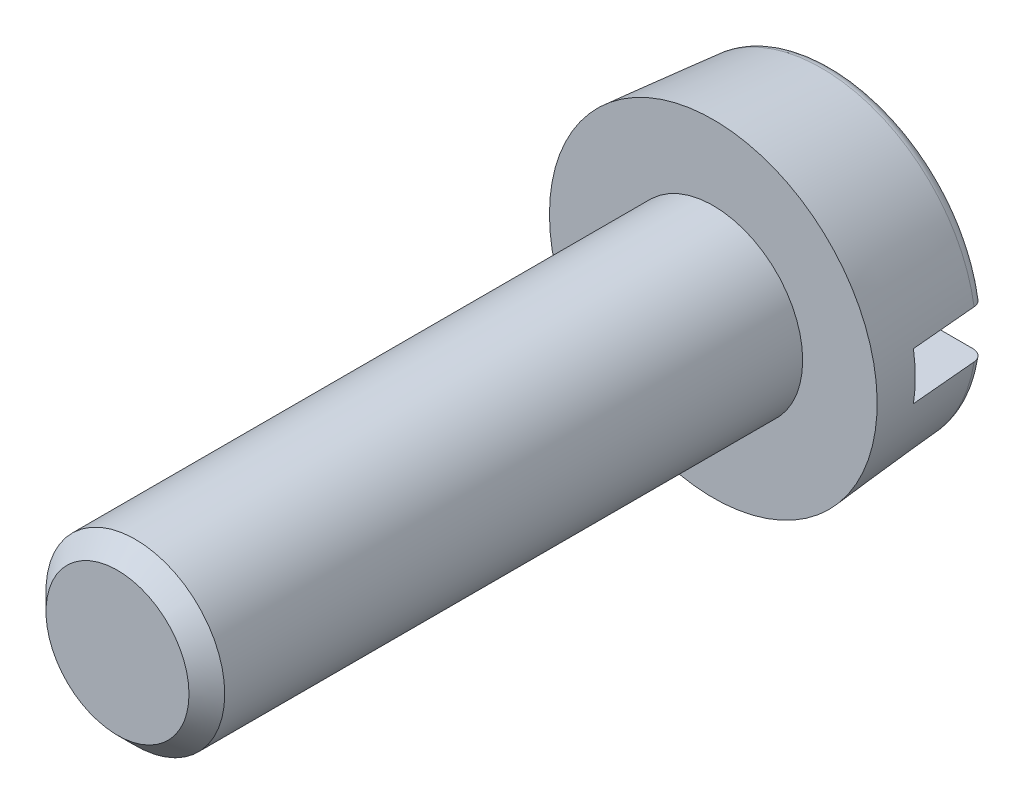
SolidWorks part; units mm, degrees
material "Acier allié"
ref_plane "Plan1" through (0, 0, 0) normal (0, 0, 1) x (1, 0, 0)
ref_plane "Plan2" through (0, 0, 0) normal (0, 1, 0) x (1, 0, 0)
ref_plane "Plan3" through (0, 0, 0) normal (1, 0, 0) x (0, 0, -1)
ref_axis "Z Axis" through (0, 0, -50) along (0, 0, 1)
sketch "Esquisse1" plane through (0, 0, 0) normal (0, 1, 0) x (1, 0, 0)
  line L0 (0, 0) -> (0, 2) construction
  line L1 (0, 0) -> (2.75, 0)
  line L2 (0, 0) -> (0, 2)
  line L3 (0, 2) -> (2.3918, 2)
  line L5 (2.75, 0) -> (2.591, 1.8174)
  arc A0 (2.3918, 2) -> (2.591, 1.8174) centre (2.3918, 1.8) cw
  dimension "D3" = 0.2
  dimension "D1" = 2.75
  dimension "D2" = 2
  dimension "D4" = 5
revolve "Base-Révolution" add sketch "Esquisse1" angle 360 about L0 reverse direction yes
sketch "Esquisse2" plane through (0, 0, -2) normal (0, 0, 1) x (1, 0, 0)
  line L1 (-2.75, 0.4) -> (2.75, 0.4)
  line L2 (-2.75, 0.4) -> (-2.75, -0.4)
  line L3 (-2.75, -0.4) -> (2.75, -0.4)
  line L4 (2.75, 0.4) -> (2.75, -0.4)
  circle A0 centre (0, 0) radius 2.75 construction
extrude "Enlev. mat.-Extru.1" cut sketch "Esquisse2" along normal blind 1.3
sketch "Esquisse3" plane through (0, 0, 0) normal (0, 1, 0) x (1, 0, 0)
  line L1 (0, 0) -> (0, -10) construction
  line L2 (0, 0) -> (1.5, 0)
  line L3 (0, 0) -> (0, -10)
  line L4 (0, -10) -> (1.5, -10)
  line L6 (1.5, 0) -> (1.5, -10)
  dimension "D1" = 10
  dimension "D2" = 1.5
revolve "Boss.-Révol.1" add sketch "Esquisse3"
cosmetic thread "Représentation de filetage1" [suppressed]
chamfer "Chanfrein1" distance 0.3 angle 45 1 edges at (1.5, 0, 10)
sketch "Esquisse4" plane through (0, 0, 0) normal (0, 1, 0) x (1, 0, 0)
  line L0 (1.195, -10.0305) -> (1.195, -9.9695)
  line L2 (1.195, -9.9695) -> (1.5305, -9.7758)
  line L3 (1.195, -10.0305) -> (1.5305, -10.2242)
  line L4 (1.5305, -9.7758) -> (1.5305, -10.2242)
  line L6 (1.5, 0) -> (1.5, -10) construction
  line L7 (0, -10) -> (1.5, -10) construction
  point P4 (1.5, -10)
  dimension "D2" = 0.0305
  dimension "D3" = 0.0305
  dimension "D4" = 0.3355
  dimension "D5" = 60
  dimension "D1" = 0.305
  dimension "D6" = 60
sketch "Esquisse5" plane through (0, 0, 10) normal (0, 0, 1) x (1, 0, 0)
  circle A0 centre (0, 0) radius 1.5 construction
  circle A1 centre (0, 0) radius 1.5
curve "Hélice1" pitch 0.5 height 9.8 turns 19.6
sweep "Enlèvement de matière-Balayage1" [suppressed] cut profiles "Esquisse4" path "Hélice1"
equation "\"D3@Esquisse1\"=\"D2@Esquisse1\"/10"
equation "\"D1@Chanfrein1\"=\"D2@Esquisse3\"*0.2"
equation "\"D3@Esquisse4\"=0.1*\"D1@Esquisse4\""
equation "\"D4@Esquisse4\"=1.1*\"D1@Esquisse4\""
equation "\"D2@Esquisse4\"=0.1*\"D1@Esquisse4\""
equation "\"D1@Esquisse4\"=0.61*\"D4@Hélice1\""
equation "\"D1@Représentation de filetage1\"=\"D3@Hélice1\""
equation "\"D2@Représentation de filetage1\"=\"D2@Esquisse3\"*1.6"
